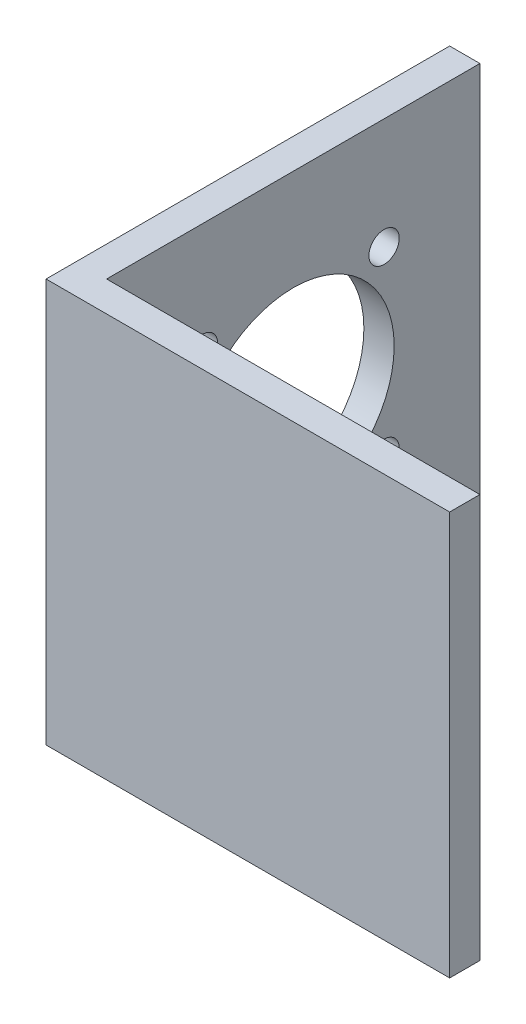
SolidWorks part; units mm, degrees
ref_plane "Спереди" through (0, 0, 0) normal (0, 0, 1) x (1, 0, 0)
ref_plane "Сверху" through (0, 0, 0) normal (0, 1, 0) x (1, 0, 0)
ref_plane "Справа" through (0, 0, 0) normal (1, 0, 0) x (0, 0, -1)
sketch "Эскиз1" plane through (0, 0, 0) normal (0, 1, 0) x (1, 0, 0)
  line L0 (0, 0) -> (40, 0)
  line L1 (40, 0) -> (40, 3)
  line L2 (40, 3) -> (3, 3)
  line L3 (3, 3) -> (3, 40)
  line L4 (3, 40) -> (0, 40)
  line L5 (0, 40) -> (0, 0)
  line L6 (1, 24.5) -> (1, 18.5) construction
  dimension "D1" = 3
  dimension "D2" = 3
  dimension "D3" = 40
  dimension "D4" = 40
  dimension "D5" = 37
extrude "Бобышка-Вытянуть1" add sketch "Эскиз1" along normal blind 40
sketch "Эскиз2" plane through (3, 0, 0) normal (1, 0, 0) x (0, 0, -1)
  line L0 (40, 0) -> (3, 40) construction
  line L1 (3, 0) -> (40, 40) construction
  line L3 (30.5, 29) -> (12.5, 29) construction
  line L4 (30.5, 29) -> (30.5, 11) construction
  line L5 (30.5, 11) -> (12.5, 11) construction
  line L6 (12.5, 29) -> (12.5, 11) construction
  line L7 (30.5, 29) -> (12.5, 11) construction
  line L8 (30.5, 11) -> (12.5, 29) construction
  circle A0 centre (21.5, 20) radius 10
  circle A1 centre (30.5, 29) radius 1.5
  circle A2 centre (30.5, 11) radius 1.5
  circle A3 centre (12.5, 11) radius 1.5
  circle A4 centre (12.5, 29) radius 1.5
  dimension "D1" = 20
  dimension "D4" = 3
  dimension "D2" = 18
  dimension "D3" = 18
extrude "Вырез-Вытянуть1" cut sketch "Эскиз2" against normal blind 40
